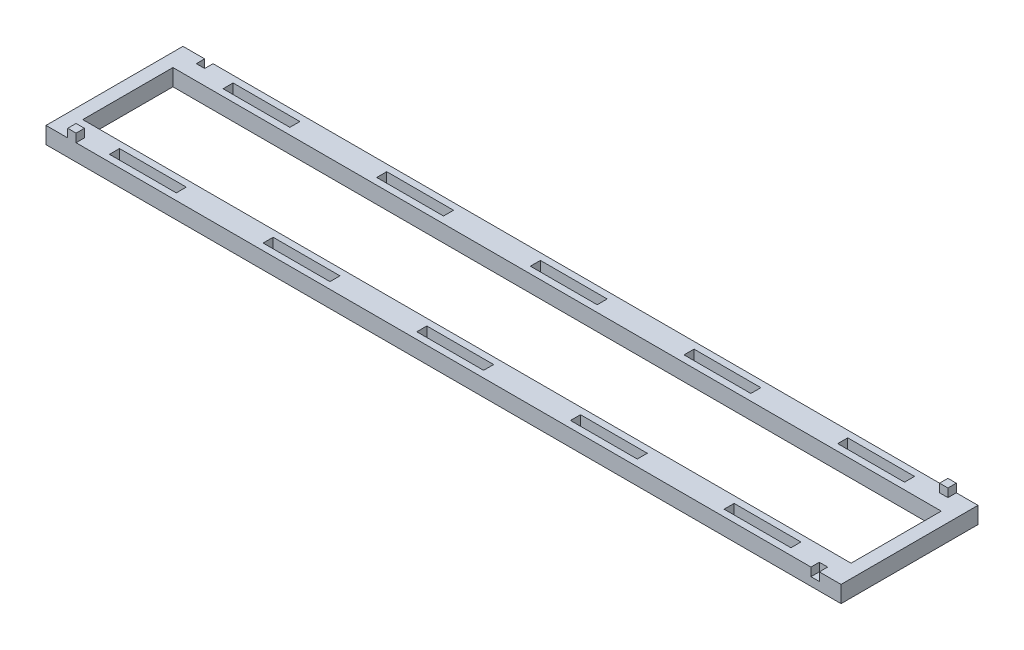
SolidWorks part; units mm, degrees
ref_plane "前视基准面" through (0, 0, 0) normal (0, 0, 1) x (1, 0, 0)
ref_plane "上视基准面" through (0, 0, 0) normal (0, 1, 0) x (1, 0, 0)
ref_plane "右视基准面" through (0, 0, 0) normal (1, 0, 0) x (0, 0, -1)
sketch "草图1" plane through (0, 0, 0) normal (0, 1, 0) x (1, 0, 0)
  line L1 (-115, 13.5) -> (115, 13.5)
  line L2 (-115, 13.5) -> (-115, -13.5)
  line L3 (-115, -13.5) -> (115, -13.5)
  line L4 (115, 13.5) -> (115, -13.5)
  line L5 (-119, 20.5) -> (119, 20.5)
  line L6 (-119, 20.5) -> (-119, -20.5)
  line L7 (-119, -20.5) -> (119, -20.5)
  line L8 (119, 20.5) -> (119, -20.5)
  point P4 (0, 13.5)
  point P5 (-115, 0)
  point P11 (119, 0)
  point P12 (115, 0)
  point P13 (0, 20.5)
  dimension "D1" = 27
  dimension "D2" = 230
  dimension "D4" = 7
  dimension "D5" = 4
extrude "凸台-拉伸1" add sketch "草图1" along normal blind 5
sketch "草图2" plane through (0, 5, 0) normal (0, 1, 0) x (1, 0, 0)
  line L0 (115, 13.5) -> (-115, 13.5) construction
  line L1 (-10, 18.5) -> (10, 18.5)
  line L2 (-10, 18.5) -> (-10, 15.5)
  line L3 (-10, 15.5) -> (10, 15.5)
  line L4 (10, 18.5) -> (10, 15.5)
  line L5 (36, 18.5) -> (36, 15.5)
  line L6 (36, 18.5) -> (56, 18.5)
  line L7 (56, 18.5) -> (56, 15.5)
  line L8 (36, 15.5) -> (56, 15.5)
  line L9 (82, 18.5) -> (82, 15.5)
  line L10 (82, 18.5) -> (102, 18.5)
  line L11 (102, 18.5) -> (102, 15.5)
  line L12 (82, 15.5) -> (102, 15.5)
  line L13 (-10, 18.5) -> (36, 18.5) construction
  point P6 (0, 15.5)
  dimension "D1" = 3
  dimension "D2" = 20
  dimension "D3" = 2
  dimension "D5" = 46
  dimension "D4" = 3
extrude "切除-拉伸1" cut sketch "草图2" against normal blind 3
mirror "镜向1" about plane through (0, 0, 0) normal (0, 0, 1) of "切除-拉伸1"
mirror "镜向2" about plane through (0, 0, 0) normal (1, 0, 0) of "切除-拉伸1", "镜向1"
sketch "草图3" plane through (0, 5, 0) normal (0, 1, 0) x (1, 0, 0)
  line L0 (119, 20.5) -> (-119, 20.5) construction
  line L1 (-112.5, 20.5) -> (-110, 20.5)
  line L2 (-112.5, 20.5) -> (-112.5, 18)
  line L3 (-112.5, 18) -> (-110, 18)
  line L4 (-110, 20.5) -> (-110, 18)
  line L5 (-119, -20.5) -> (119, -20.5) construction
  line L6 (-112.5, -20.5) -> (-110, -20.5)
  line L7 (-112.5, -20.5) -> (-112.5, -18)
  line L8 (-112.5, -18) -> (-110, -18)
  line L9 (-110, -20.5) -> (-110, -18)
  line L11 (110, 20.5) -> (112.5, 20.5)
  line L12 (110, 20.5) -> (110, 18)
  line L13 (110, 18) -> (112.5, 18)
  line L14 (112.5, 20.5) -> (112.5, 18)
  line L15 (112.5, -20.5) -> (110, -20.5)
  line L16 (112.5, -20.5) -> (112.5, -18)
  line L17 (112.5, -18) -> (110, -18)
  line L18 (110, -20.5) -> (110, -18)
  line M38 (-119, -20.5) -> (119, -20.5)
  line M40 (119, 20.5) -> (-119, 20.5)
  dimension "D1" = 2.5
  dimension "D2" = 110
  dimension "D3" = 110
extrude "凸台-拉伸2" add sketch "草图3" along normal blind 2.5 contours L9 L8 L7 M38 | L14 L12 L13 M40 region at (111.25, 5, -19.25) region at (-111.25, 5, 19.25)
extrude "切除-拉伸2" cut sketch "草图3<3>" against normal blind 2.5 contours L4 L2 L3 M40 | L17 L18 L15 L16 region at (-111.25, 5, -19.25)
sketch "草图3<3>" plane through (0, 5, 0) normal (0, 1, 0) x (1, 0, 0) same geometry as "草图3"
